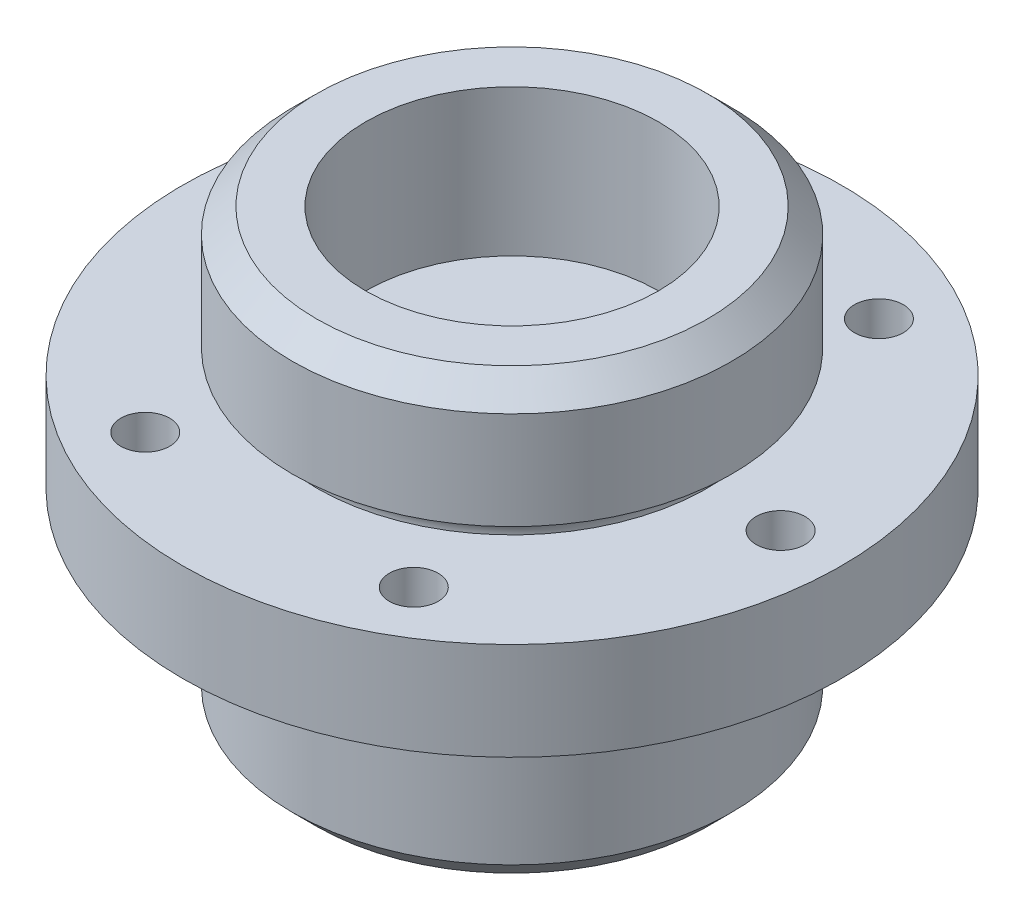
SolidWorks part; units mm, degrees
note: The reader was unsure of these and kept them because the rebuilt part matched: shared geometry of "Çizim1<3>".
ref_plane "Ön Düzlem" through (0, 0, 0) normal (0, 0, 1) x (1, 0, 0)
ref_plane "Üst Düzlem" through (0, 0, 0) normal (0, 1, 0) x (1, 0, 0)
ref_plane "Sağ Düzlem" through (0, 0, 0) normal (1, 0, 0) x (0, 0, -1)
sketch "Çizim1" plane through (0, 0, 0) normal (0, 1, 0) x (1, 0, 0)
  circle A0 centre (0, 0) radius 24
  circle A1 centre (0, 0) radius 36
  circle A2 centre (0, 0) radius 54
  dimension "D1" = 48
  dimension "D2" = 72
  dimension "D3" = 108
extrude "Yükseklik-Ekstrüzyon1" add sketch "Çizim1" along normal blind 40 and the other way blind 32 contours A1 A0
extrude "Yükseklik-Ekstrüzyon2" add sketch "Çizim1<3>" along normal blind 16 contours A2
sketch "Çizim1<3>" plane through (0, 0, 0) normal (0, 1, 0) x (1, 0, 0) same geometry as "Çizim1"
chamfer "Pah1" distance 4 angle 45 1 edges at (0, 40, 36)
chamfer "Pah3" distance 4 angle 45 1 edges at (0, -32, 36)
sketch "Çizim4" plane through (0, 0, 0) normal (1, 0, 0) x (0, 0, -1)
  line L0 (-36, 36) -> (-36, 16) construction
  line L1 (54, 16) -> (-54, 16) construction
  line L2 (-36, 20) -> (-36, 16)
  line L3 (-36, 16) -> (-32, 16)
  arc A0 (-36, 20) -> (-32, 16) centre (-36, 16) cw
  dimension "D2" = 4
sweep "Kes-Süpür1" cut profiles "Çizim4" path edge at (0, 16, 36)
sketch "Çizim5" plane through (0, 0, 0) normal (1, 0, 0) x (0, 0, -1)
  line L0 (-36, 0) -> (-36, -28) construction
  line L1 (-36, 0) -> (36, 0) construction
  line L2 (-36, 0) -> (-36, -4)
  line L3 (-32, 0) -> (-36, 0)
  arc A0 (-36, -4) -> (-32, 0) centre (-36, 0) ccw
  dimension "D1" = 4
sweep "Kes-Süpür3" cut profiles "Çizim5" path edge at (0, 0, 36)
sketch "Çizim6" plane through (0, 16, 0) normal (0, 1, 0) x (1, 0, 0)
  circle A1 centre (-22, 38.1051) radius 4
  circle A3 centre (22, 38.1051) radius 4
  circle A4 centre (44, 0) radius 4
  circle A5 centre (22, -38.1051) radius 4
  circle A6 centre (-22, -38.1051) radius 4
  circle A7 centre (-44, 0) radius 4
  dimension "D2" = 8
  dimension "D4" = 6
extrude "Kes-Ekstrüzyon1" cut sketch "Çizim6" against normal blind 16
